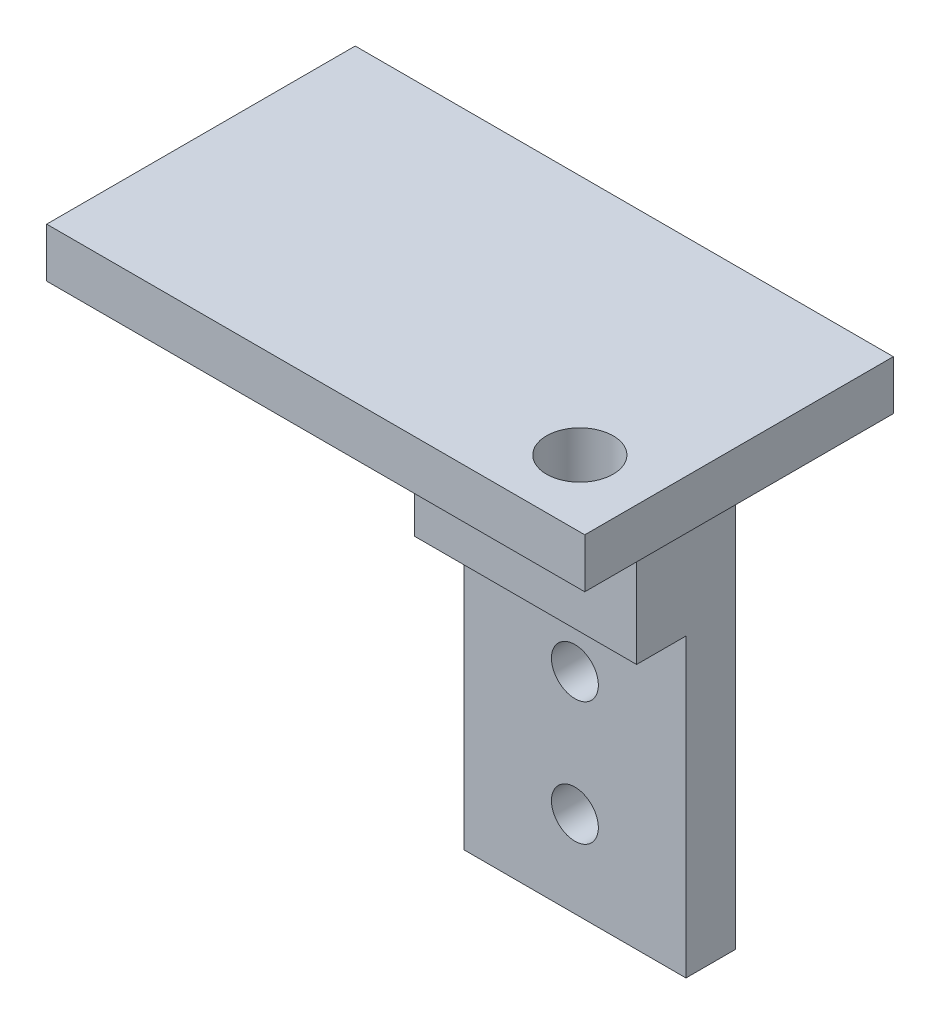
SolidWorks part; units mm, degrees
ref_plane "Front Plane" through (0, 0, 0) normal (0, 0, 1) x (1, 0, 0)
ref_plane "Top Plane" through (0, 0, 0) normal (0, 1, 0) x (1, 0, 0)
ref_plane "Right Plane" through (0, 0, 0) normal (1, 0, 0) x (0, 0, -1)
ref_axis "X-Axis" through (-88.99, 0, 0) along (1, 0, 0)
ref_axis "Y-Axis" through (0, 55, 0) along (0, -1, 0)
ref_axis "Z-Axis" through (0, 0, -88.99) along (0, 0, 1)
sketch "Sketch1" plane through (0, 0, 0) normal (0, 1, 0) x (1, 0, 0)
  line L1 (-10.9, 6.25) -> (10.9, 6.25)
  line L2 (-10.9, 6.25) -> (-10.9, -6.25)
  line L3 (-10.9, -6.25) -> (10.9, -6.25)
  line L4 (10.9, 6.25) -> (10.9, -6.25)
  line L5 (-10.9, 6.25) -> (10.9, -6.25) construction
  line L6 (-10.9, -6.25) -> (10.9, 6.25) construction
  point P0 (0, 0)
  dimension "D1" = 12.5
  dimension "D2" = 21.8
extrude "Boss-Extrude1" add sketch "Sketch1" along normal blind 2
sketch "Sketch2" plane through (0, 2, 0) normal (0, 1, 0) x (1, 0, 0)
  line L0 (10.9, -6.25) -> (10.9, 6.25) construction
  line L1 (-10.9, -6.25) -> (10.9, -6.25) construction
  circle A0 centre (8, -3.55) radius 1.8
  point P2 (9.8, -3.55)
  point P3 (8, -5.35)
  dimension "D3" = 3.6
  dimension "D1" = 1.1
  dimension "D2" = 0.9
extrude "Cut-Extrude1" cut sketch "Sketch2" against normal up to next
sketch "Sketch3" plane through (0, 0, 0) normal (0, -1, 0) x (1, 0, 0)
  line L0 (10.9, -6.25) -> (-10.9, -6.25) construction
  line L1 (-4.5, -6.25) -> (4.5, -6.25)
  line L2 (-4.5, -6.25) -> (-4.5, -4.25)
  line L3 (-4.5, -4.25) -> (4.5, -4.25)
  line L4 (4.5, -6.25) -> (4.5, -4.25)
  line L5 (-10.9, -6.25) -> (-4.5, -6.25) construction
  line L6 (4.5, -6.25) -> (10.9, -6.25) construction
  dimension "D1" = 2
  dimension "D2" = 9
extrude "Boss-Extrude2" add sketch "Sketch3" along normal blind 22
sketch "Sketch4" plane through (0, 0, -6.25) normal (0, 0, -1) x (-1, 0, 0)
  line L0 (0, -22) -> (0, 0) construction
  line L1 (4.5, -22) -> (-4.5, -22) construction
  circle A0 centre (0, -13.5) radius 0.95
  circle A1 centre (0, -18.5) radius 0.95
  dimension "D1" = 1.9
  dimension "D2" = 5
  dimension "D3" = 3.5
extrude "Cut-Extrude2" cut sketch "Sketch4" against normal through all
sketch "Sketch5" plane through (0, 2, 0) normal (0, 1, 0) x (1, 0, 0)
  circle A0 centre (8, -3.55) radius 1.35
  circle A3 centre (8, -3.55) radius 1.8
  circle A4 centre (8, -3.55) radius 1.8
  dimension "D1" = 2.7
  dimension "D2" = 0
extrude "Boss-Extrude3" add sketch "Sketch5" against normal up to surface (2 mm away) up to face at (8, 0, 5.35)
sketch "Sketch6" plane through (0, 0, 0) normal (0, -1, 0) x (1, 0, 0)
  line L1 (-4.5, -4.25) -> (4.5, -4.25)
  line L2 (-4.5, -4.25) -> (-4.5, -2.25)
  line L3 (-4.5, -2.25) -> (4.5, -2.25)
  line L4 (4.5, -4.25) -> (4.5, -2.25)
  dimension "D1" = 2
extrude "Boss-Extrude4" add sketch "Sketch6" along normal blind 10
